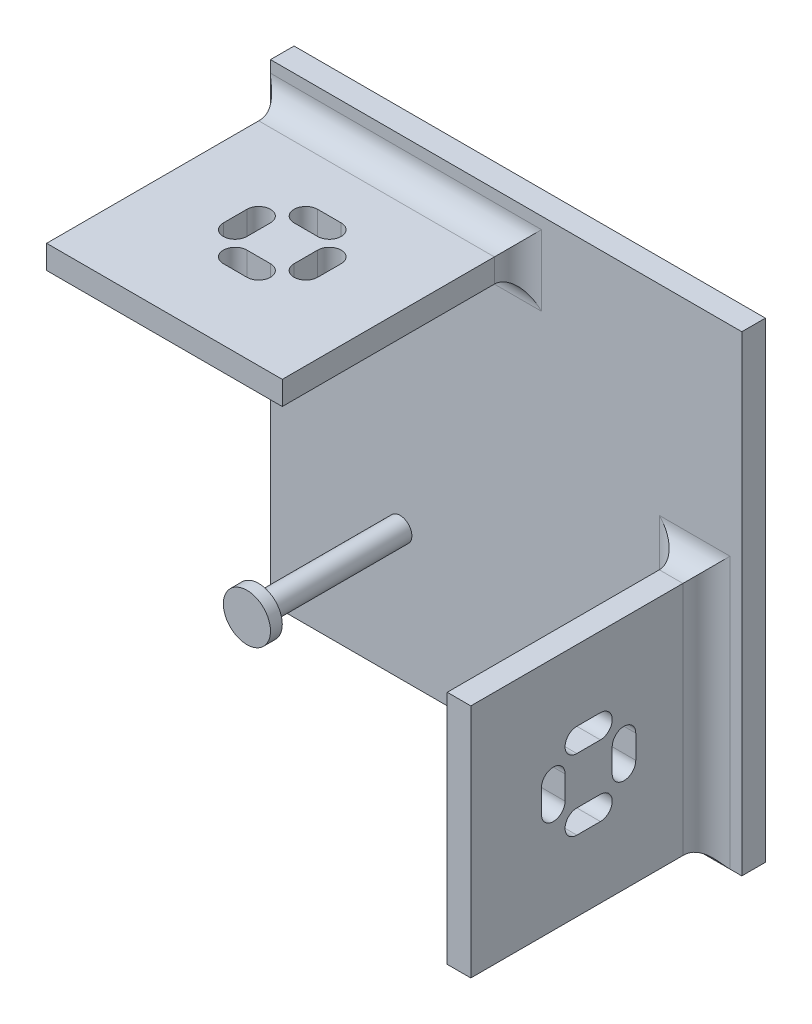
SolidWorks part; units mm, degrees
ref_plane "Front Plane" through (0, 0, 0) normal (0, 0, 1) x (1, 0, 0)
ref_plane "Top Plane" through (0, 0, 0) normal (0, 1, 0) x (1, 0, 0)
ref_plane "Right Plane" through (0, 0, 0) normal (1, 0, 0) x (0, 0, -1)
sketch "Sketch1" plane through (0, 0, 0) normal (0, 0, 1) x (1, 0, 0)
  line L1 (-25.4, -25.4) -> (25.4, -25.4)
  line L2 (-25.4, -25.4) -> (-25.4, 25.4)
  line L3 (-25.4, 25.4) -> (25.4, 25.4)
  line L4 (25.4, -25.4) -> (25.4, 25.4)
  line L5 (-25.4, -25.4) -> (25.4, 25.4) construction
  line L6 (-25.4, 25.4) -> (25.4, -25.4) construction
  point P0 (0, 0)
  dimension "D1" = 50.8
  dimension "D2" = 50.8
extrude "base" add sketch "Sketch1" along normal blind 2.54
sketch "Sketch2" plane through (0, 0, 2.54) normal (0, 0, 1) x (1, 0, 0)
  circle A0 centre (-11.43, -11.43) radius 1.27
  dimension "D1" = 2.54
extrude "post for wing" add sketch "Sketch2" along normal blind 15.24
sketch "Sketch4" plane through (0, 0, 2.54) normal (0, 0, 1) x (1, 0, 0)
  line L1 (-24.13, 19.05) -> (1.27, 19.05)
  line L2 (-24.13, 19.05) -> (-24.13, 21.59)
  line L3 (-24.13, 21.59) -> (1.27, 21.59)
  line L4 (1.27, 19.05) -> (1.27, 21.59)
  line L5 (-24.13, 19.05) -> (1.27, 21.59) construction
  line L6 (-24.13, 21.59) -> (1.27, 19.05) construction
  point P0 (-11.43, 20.32)
  dimension "D1" = 2.54
  dimension "D2" = 25.4
extrude "button holder" add sketch "Sketch4" along normal blind 25.4
ref_point "centre of button"
ref_axis "button axis" through (-11.43, 21.59, 15.24) along (0, 1, 0)
sketch "Sketch6" plane through (0, 21.59, 0) normal (0, 1, 0) x (1, 0, 0)
  line L0 (-12.7, -19.05) -> (-10.16, -19.05) construction
  line L1 (-12.7, -17.78) -> (-10.16, -17.78)
  line L2 (-12.7, -20.32) -> (-10.16, -20.32)
  arc A0 (-12.7, -17.78) -> (-12.7, -20.32) centre (-12.7, -19.05) ccw
  arc A1 (-10.16, -20.32) -> (-10.16, -17.78) centre (-10.16, -19.05) ccw
  point P2 (-11.43, -19.05)
  dimension "D2" = 1.27
  dimension "D1" = 2.54
  dimension "D3" = 0
  dimension "D4" = 3.81
extrude "one button leg hole" cut sketch "Sketch6" against normal blind 6.35
pattern_circular "moar leg holes" count 4 over 360 about axis through (-11.43, 21.59, 15.24) along (0, 1, 0) of "one button leg hole"
fillet "make everything not break" radius 2.54 4 edges at (1.27, 20.32, 2.54) (-11.43, 19.05, 2.54) (-11.43, 21.59, 2.54) (-24.13, 20.32, 2.54)
ref_axis "rotate for second button" through (-11.43, -11.43, 17.78) along (0, 0, -1)
pattern_circular "second button" count 2 every 90 about axis through (-11.43, -11.43, 17.78) along (0, 0, -1) of "button holder", "one button leg hole", "moar leg holes", "make everything not break"
sketch "Sketch3" plane through (0, 0, 17.78) normal (0, 0, 1) x (1, 0, 0)
  circle A0 centre (-11.43, -11.43) radius 2.54
  dimension "D1" = 5.08
extrude "don't let it fall off" add sketch "Sketch3" along normal blind 1.27
